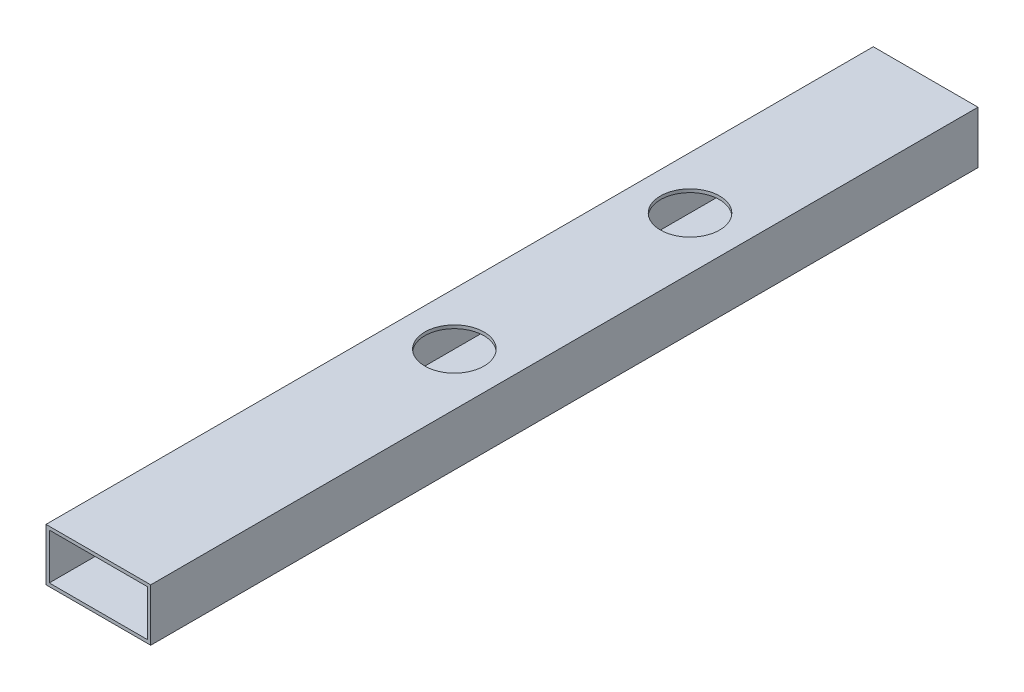
SolidWorks part; units mm, degrees
ref_plane "Front Plane" through (0, 0, 0) normal (0, 0, 1) x (1, 0, 0)
ref_plane "Top Plane" through (0, 0, 0) normal (0, 1, 0) x (1, 0, 0)
ref_plane "Right Plane" through (0, 0, 0) normal (1, 0, 0) x (0, 0, -1)
sketch "Sketch1" plane through (0, 0, 0) normal (0, 0, 1) x (1, 0, 0)
  line L0 (1.5875, 1.5875) -> (1.5875, 23.8125)
  line L1 (0, 0) -> (50.8, 0)
  line L2 (0, 0) -> (0, 25.4)
  line L3 (0, 25.4) -> (50.8, 25.4)
  line L4 (50.8, 0) -> (50.8, 25.4)
  line L5 (1.5875, 23.8125) -> (49.2125, 23.8125)
  line L6 (49.2125, 1.5875) -> (49.2125, 23.8125)
  line L7 (1.5875, 1.5875) -> (49.2125, 1.5875)
  dimension "D1" = 25.4
  dimension "D2" = 50.8
  dimension "D3" = 1.5875
extrude "Boss-Extrude1" add sketch "Sketch1" along normal blind 401.32
sketch "Sketch2" plane through (0, 25.4, 0) normal (0, 1, 0) x (1, 0, 0)
  line L0 (50.8, 0) -> (0, 0) construction
  line L2 (50.8, -401.32) -> (50.8, 0) construction
  circle A0 centre (25.4, -114.3) radius 14.351
  circle A1 centre (25.4, -228.6) radius 14.351
  dimension "D1" = 28.702
  dimension "D2" = 28.702
  dimension "D3" = 114.3
  dimension "D4" = 114.3
  dimension "D5" = 25.4
  dimension "D6" = 25.4
extrude "Cut-Extrude1" cut sketch "Sketch2" against normal through all
